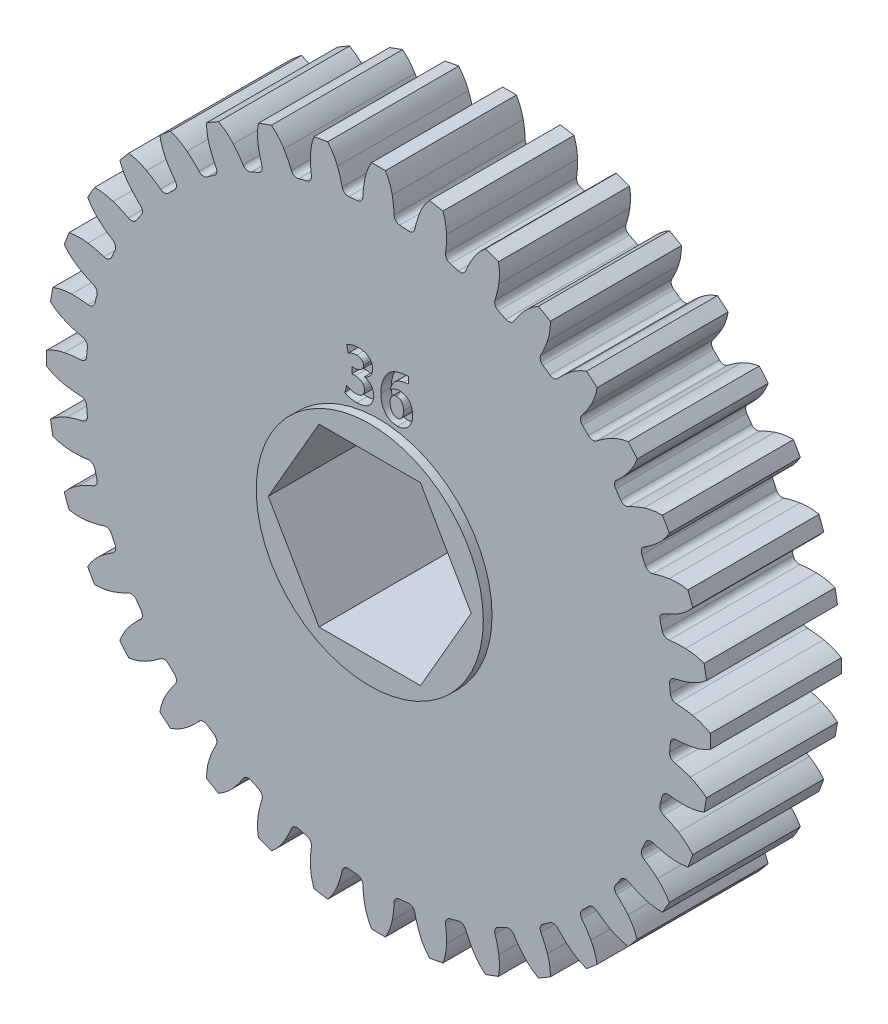
SolidWorks part; units mm, degrees
other "DetailItem7"
other "DetailItem8"
material "PLA/ABS"
ref_plane "Front" through (0, 0, 0) normal (0, 0, 1) x (1, 0, 0)
ref_plane "Top" through (0, 0, 0) normal (0, 1, 0) x (1, 0, 0)
ref_plane "Right" through (0, 0, 0) normal (1, 0, 0) x (0, 0, -1)
sketch "Sketch1" plane through (0, 0, 0) normal (0, 0, 1) x (1, 0, 0)
  line L0 (0, 0) -> (22.86, 0) construction
  line L1 (22.86, 0) -> (24.13, 0) construction
  circle A0 centre (0, 0) radius 22.86 construction
  circle A1 centre (0, 0) radius 24.13
  dimension "D1" = 45.72
  dimension "D2" = 1.27
extrude "Round Stock" add sketch "Sketch1" along normal mid plane 9.525
sketch "Sketch2" plane through (0, 0, 4.7625) normal (0, 0, 1) x (1, 0, 0)
  line L0 (0, 0) -> (21.2725, 0) construction
  line L1 (21.2725, 0) -> (22.86, 0) construction
  line L2 (0, 0) -> (-24.13, 0) construction
  line L3 (0, 0) -> (-23.7634, -4.1901) construction
  line L4 (-23.8457, -3.6931) -> (-22.6645, -2.9834) construction
  line L5 (-22.6645, -2.9834) -> (-21.1219, -2.5265) construction
  line L6 (-24.1247, -0.5038) -> (-22.8382, -0.9976) construction
  line L7 (-22.8382, -0.9976) -> (-21.2398, -1.1797) construction
  line L8 (-22.4913, -3.9658) -> (-22.6645, -2.9834) construction
  line L9 (-22.8382, -0.9976) -> (-22.8382, 0) construction
  line L12 (0, 0) -> (-22.8382, -0.9976) construction
  line L13 (0, 0) -> (-22.6645, -2.9834) construction
  line L14 (-22.6645, -2.9834) -> (-21.6563, -10.6424) construction
  line L15 (-22.8382, -0.9976) -> (-23.1753, 6.7202) construction
  line L16 (-22.6645, -2.9834) -> (-22.8382, -0.9976) construction
  line L17 (-21.1916, -1.854) -> (-21.2398, -1.1797) construction
  line L18 (-21.1916, -1.854) -> (-21.1219, -2.5265) construction
  circle A0 centre (0, 0) radius 22.86 construction
  circle A1 centre (0, 0) radius 21.2725 construction
  circle A2 centre (0, 0) radius 24.13 construction
  arc A3 (-23.8457, -3.6931) -> (-24.1247, -0.5038) centre (0, 0) cw
  arc A4 (-21.1219, -2.5265) -> (-21.2398, -1.1797) centre (0, 0) cw construction
  arc A6 (-23.8457, -3.6931) -> (-22.6645, -2.9834) centre (-21.2309, -6.7073) cw
  arc A7 (-24.1247, -0.5038) -> (-22.8382, -0.9976) centre (-22.073, 2.9187) ccw
  arc A8 (-22.6645, -2.9834) -> (-21.5117, -2.6406) centre (-19.907, -10.1461) cw
  arc A9 (-22.8382, -0.9976) -> (-21.6435, -1.135) centre (-21.3664, 6.5351) ccw
  arc A10 (-21.5117, -2.6406) -> (-21.1625, -2.1607) centre (-21.6047, -2.2059) ccw
  arc A11 (-21.6435, -1.135) -> (-21.2162, -1.5469) centre (-21.6595, -1.5792) cw
  arc A12 (-21.1625, -2.1607) -> (-21.2162, -1.5469) centre (0, 0) cw
  dimension "D6" = 45.72
  dimension "D9" = 0.4445
  dimension "D12" = 3.9903
  dimension "D2" = 1.5875
  dimension "D3" = 10
  dimension "D4" = 0.9976
  dimension "D5" = 0.9976
  dimension "D11" = 1.9934
  dimension "D8" = 14.5
  dimension "D7" = 14.5
  dimension "D14" = 9
  dimension "D15" = 9
extrude "Single Tooth" cut sketch "Sketch2" against normal through all
ref_axis "Axis" through (0, 0, 50) along (0, 0, -1)
pattern_circular "Tooth Pattern" count 36 over 360 about axis through (0, 0, 50) along (0, 0, -1) of "Single Tooth"
sketch "Sketch4" plane through (0, 0, 4.7625) normal (0, 0, 1) x (1, 0, 0)
  circle A0 centre (0, 0) radius 8.255
  dimension "D1" = 16.51
extrude "TopBearingBoss" add sketch "Sketch4" along normal blind 0.635
mirror "BottomBearingBoss" about plane through (0, 0, 0) normal (0, 0, 1) of "TopBearingBoss"
sketch "Sketch5" plane through (0, 0, 0) normal (0, 0, 1) x (1, 0, 0)
  circle A0 centre (0, 0) radius 6.3881
  dimension "D1" = 12.7762
extrude "RoundBore" cut sketch "Sketch5" against normal through all both and the other way through all
sketch "Sketch6" plane through (0, 0, 0) normal (0, 0, 1) x (1, 0, 0)
  line L1 (3.6882, 6.3881) -> (-3.6882, 6.3881)
  line L2 (-3.6882, 6.3881) -> (-7.3763, 0)
  line L3 (-7.3763, 0) -> (-3.6882, -6.3881)
  line L4 (-3.6882, -6.3881) -> (3.6882, -6.3881)
  line L5 (3.6882, -6.3881) -> (7.3763, 0)
  line L6 (7.3763, 0) -> (3.6882, 6.3881)
  circle A0 centre (0, 0) radius 6.3881 construction
  circle A1 centre (0, 0) radius 6.3881 construction
extrude "Hex" cut sketch "Sketch6" against normal through all both and the other way through all
sketch "Sketch7" plane through (0, 0, 4.7625) normal (0, 0, 1) x (1, 0, 0)
  line L0 (-10.955, 8.509) -> (10.955, 8.509) construction
  line L1 (0, 0) -> (0, 8.509) construction
  text T0 "36" font "Adobe Gothic Std B" height 3.5
  dimension "D1" = 8.509
extrude "ToothCount" cut sketch "Sketch7" against normal blind 0.762
equation "\"N_teeth\"= \"No_Teeth\""
equation "\"pitch_diameter\"= \"N_teeth\" / \"Pitch\""
equation "\"Pd\"=\"N_teeth\"/\"pitch_diameter\""
equation "\"addendum\"=1.000/\"Pd\""
equation "\"face_width\"=0.375000"
equation "\"deddendum\"=1.250/\"Pd\""
equation "\"D3@Sketch2\" = 360/\"N_teeth\""
equation "\"tooth_thickness\"=1.571/\"Pd\""
equation "\"D4@Sketch2\" = \"tooth_thickness\"/2"
equation "\"D5@Sketch2\" = \"tooth_thickness\"/2"
equation "\"Pressure_Angle\"= iif ( \"Pitch\" = 20 , 14.500000 , iif ( \"Pitch\" = 32 , 20 , 20 ) )"
equation "\"base_fillet\"=0.35/\"Pd\""
equation "\"D12@Sketch2\" = 2*\"tooth_thickness\""
equation "\"hub_projection\"=0.250000"
equation "\"sss_diam\"= 0.062500"
equation "\"D1@Sketch1\"=\"pitch_diameter\""
equation "\"D2@Sketch1\"=\"addendum\""
equation "\"D1@Round Stock\" = \"face_width\""
equation "\"D2@Sketch2\"=\"deddendum\""
equation "\"D6@Sketch2\"=\"pitch_diameter\""
equation "\"D7@Sketch2\"=\"Pressure_Angle\""
equation "\"D8@Sketch2\"=\"D7@Sketch2\""
equation "\"D9@Sketch2\"=\"base_fillet\""
equation "\"D1@Tooth Pattern\" = \"N_teeth\""
equation "\"Pitch\"= \"GearPitch\""
equation "\"BossDia\"= \"BoreDia\" * 1.3"
equation "\"D1@Sketch5\"=\"BoreDia\"+\"PrintTol\""
equation "\"Hex\"= iif ( \"HexBore\" = 1 , \"unsuppressed\" , \"suppressed\" )"
equation "\"TopBearingBoss\" = iif ( \"Bearing_Boss\" = 0 , \"suppressed\" , \"unsuppressed\" )"
equation "\"BottomBearingBoss\"= iif ( \"Bearing_Boss\" > 1 , \"unsuppressed\" , \"suppressed\" )"
equation "\"D1@Sketch4\"=\"BossDia\""
equation "\"D1@Sketch7\"=\"BossDia\"/2+.01"
equation "\"ToothCount\"= iif ( \"No_Teeth\" < 22 , \"suppressed\" , \"unsuppressed\" )"
